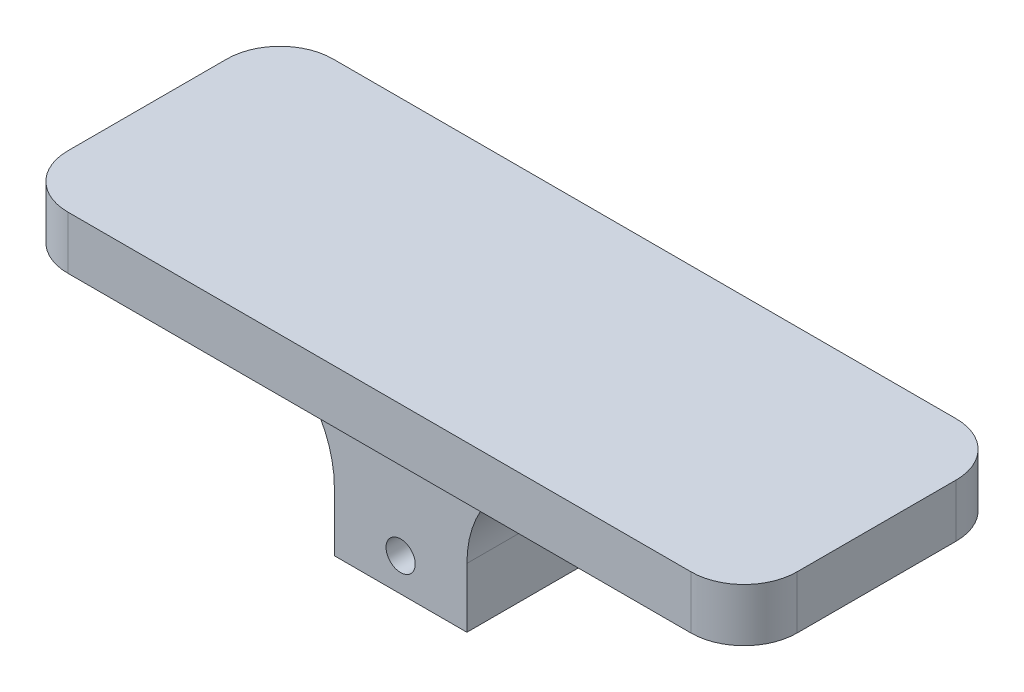
SolidWorks part; units mm, degrees
ref_plane "前视基准面" through (0, 0, 0) normal (0, 0, 1) x (1, 0, 0)
ref_plane "上视基准面" through (0, 0, 0) normal (0, 1, 0) x (1, 0, 0)
ref_plane "右视基准面" through (0, 0, 0) normal (1, 0, 0) x (0, 0, -1)
sketch "草图1" plane through (0, 0, 0) normal (0, 1, 0) x (1, 0, 0)
  line L1 (27.5, -10) -> (-27.5, -10)
  line L2 (27.5, -10) -> (27.5, 10)
  line L3 (27.5, 10) -> (-27.5, 10)
  line L4 (-27.5, -10) -> (-27.5, 10)
  line L5 (27.5, -10) -> (-27.5, 10) construction
  line L6 (27.5, 10) -> (-27.5, -10) construction
  point P0 (0, 0)
  dimension "D1" = 55
  dimension "D2" = 20
extrude "凸台-拉伸1" add sketch "草图1" along normal blind 4
sketch "草图2" plane through (0, 0, 0) normal (0, -1, 0) x (1, 0, 0)
  line L0 (9.075, 0) -> (-9.075, 0) construction
  line L1 (-27.5, -10) -> (-27.5, 10) construction
  circle A0 centre (-22.5, 0) radius 3
  dimension "D1" = 6
  dimension "D2" = 5
extrude "切除-拉伸1" cut sketch "草图2" against normal blind 2.5
sketch "草图3" plane through (0, 2.5, 0) normal (0, -1, 0) x (1, 0, 0)
  circle A0 centre (-22.5, 0) radius 2
  dimension "D1" = 4
extrude "凸台-拉伸2" add sketch "草图3" along normal blind 3.5
sketch "草图5" plane through (0, 0, 0) normal (0, 0, 1) x (1, 0, 0)
  line L0 (-2.5, -1.2697) -> (-2.5, 49998.7303) construction
  line L1 (-27.5, 4) -> (-27.5, 0) construction
  line L2 (-7.5, 0) -> (-7.5, -12.5)
  line L3 (27.5, 0) -> (-27.5, 0) construction
  line L4 (-7.5, -12.5) -> (2.5, -12.5)
  line L5 (2.5, 0) -> (2.5, -12.5)
  line L6 (2.5, 0) -> (-7.5, 0)
  circle A0 centre (-2.5, -10) radius 1.1
  point P11 (-2.5, -12.5)
  dimension "D4" = 2.2
  dimension "D1" = 25
  dimension "D2" = 12.5
  dimension "D3" = 5
  dimension "D5" = 2.5
extrude "凸台-拉伸3" add sketch "草图5" along normal mid plane 11.8
fillet "圆角1" radius 8 2 edges at (2.5, 0, 0) (-7.5, 0, 0)
fillet "圆角2" radius 4 4 edges at (27.5, 2, -10) (27.5, 2, 10) (-27.5, 2, 10) (-27.5, 2, -10)
